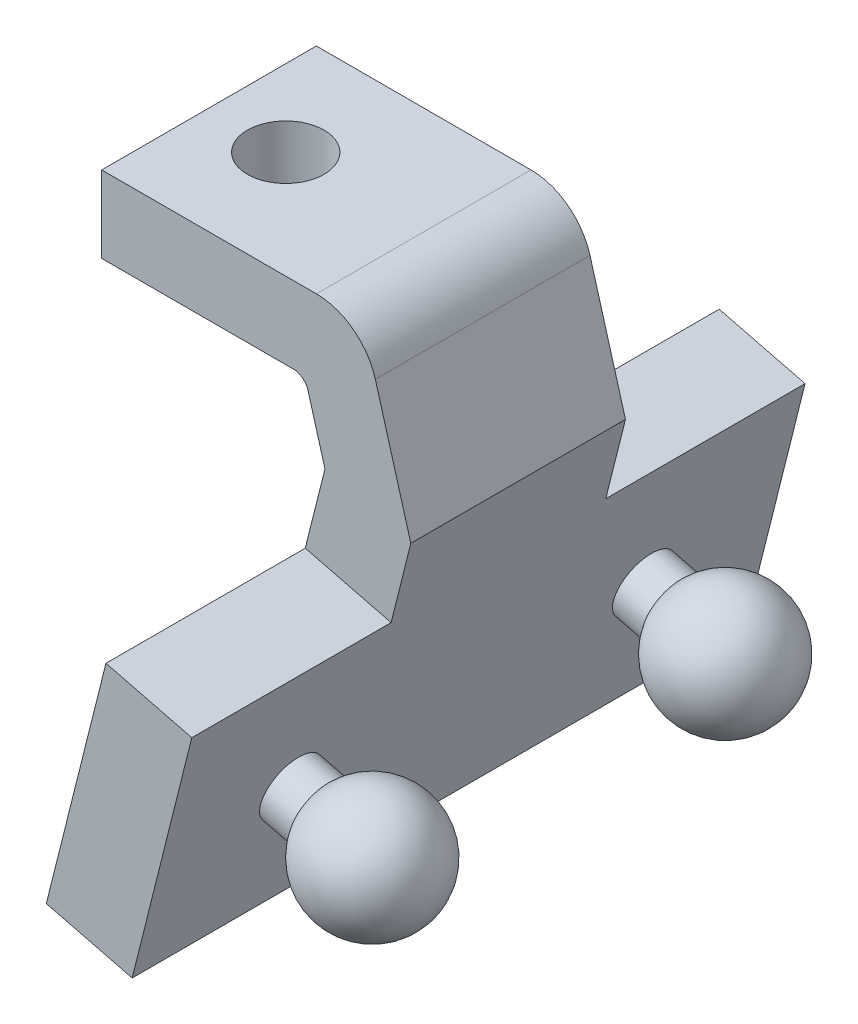
SolidWorks part; units mm, degrees
ref_plane "前视基准面" through (0, 0, 0) normal (0, 0, 1) x (1, 0, 0)
ref_plane "上视基准面" through (0, 0, 0) normal (0, 1, 0) x (1, 0, 0)
ref_plane "右视基准面" through (0, 0, 0) normal (1, 0, 0) x (0, 0, -1)
other "Configuration Table"
sketch "草图1" plane through (0, 0, 0) normal (0, 0, 1) x (1, 0, 0)
  line L0 (0, 0) -> (6.2454, 0)
  line L1 (6.7262, -0.3628) -> (7.2802, -2.304)
  line L2 (7.2802, -2.304) -> (4.6928, -12.6245)
  line L3 (4.6928, -12.6245) -> (7.4929, -13.3265)
  line L4 (7.4929, -13.3265) -> (10.0803, -3.006)
  line L5 (10.0803, -3.006) -> (8.9232, 1.0488)
  line L6 (0, 2.5) -> (7, 2.5)
  line L7 (0, 0) -> (0, 2.5)
  arc A0 (6.2454, 0) -> (6.7262, -0.3628) centre (6.2454, -0.5) cw
  arc A1 (8.9232, 1.0488) -> (7, 2.5) centre (7, 0.5) ccw
  dimension "D1" = 7
  dimension "D3" = 2
  dimension "D6" = 0.5
  dimension "D2" = 2.5
  dimension "D4" = 150
  dimension "D5" = 2.5
extrude "凸台-拉伸1" add sketch "草图1" along normal mid plane 7
sketch "草图2" plane through (0, 0, 0) normal (0, -1, 0) x (1, 0, 0)
  circle A0 centre (2.5, 0) radius 1.25
  dimension "D1" = 2.5
  dimension "D2" = 2.5
extrude "切除-拉伸3" cut sketch "草图2" against normal blind 5.5
sketch "草图3" plane through (10.1932, -2.5554, 0) normal (0.97, -0.2432, 0) x (0, 0, -1)
  line L0 (-3.5, -11.1044) -> (3.5, -11.1044) construction
  line L1 (-10, -3.1044) -> (10, -3.1044)
  line L2 (-10, -3.1044) -> (-10, -11.1044)
  line L3 (-10, -11.1044) -> (10, -11.1044)
  line L4 (10, -3.1044) -> (10, -11.1044)
  line L5 (-10, -3.1044) -> (10, -11.1044) construction
  line L6 (-10, -11.1044) -> (10, -3.1044) construction
  point P0 (0, -7.1044)
  dimension "D1" = 20
  dimension "D2" = 8
extrude "凸台-拉伸2" add sketch "草图3" against normal up to vertex (2.8868 mm away) up to point (7.2802, -2.304, -3.5)
sketch "草图4" plane through (10.1932, -2.5554, 0) normal (0.97, -0.2432, 0) x (0, 0, -1)
  circle A0 centre (-5.7543, -7.2566) radius 1
  point P2 (-5.791, -6.9263)
  point P3 (-5.7543, -7.2566)
  dimension "D1" = 2
extrude "凸台-拉伸3" add sketch "草图4" along normal blind 1
ref_axis "基准轴1" through (9.3412, -9.823, 5.7543) along (-0.97, 0.2432, 0)
ref_plane "基准面1" through (-1.7646, -7.0387, 0) normal (0.2432, 0.97, 0) x (-0.97, 0.2432, 0)
sketch "草图5" plane through (-1.7646, -7.0387, 0) normal (0.2432, 0.97, 0) x (-0.97, 0.2432, 0)
  line L0 (-11.5087, 5.7543) -> (-15.2407, 5.7543)
  line L1 (-11.5087, 6.7543) -> (-11.5087, 4.7543) construction
  line L2 (-11.5087, 5.7543) -> (-11.5087, 6.7543)
  arc A0 (-11.5087, 6.7543) -> (-15.2407, 5.7543) centre (-13.2407, 5.7543) ccw
  dimension "D1" = 4
revolve "旋转1" add sketch "草图5" angle 360 about L0
mirror "镜向1" about plane through (0, 0, 0) normal (0, 0, 1) of "凸台-拉伸3", "旋转1"
